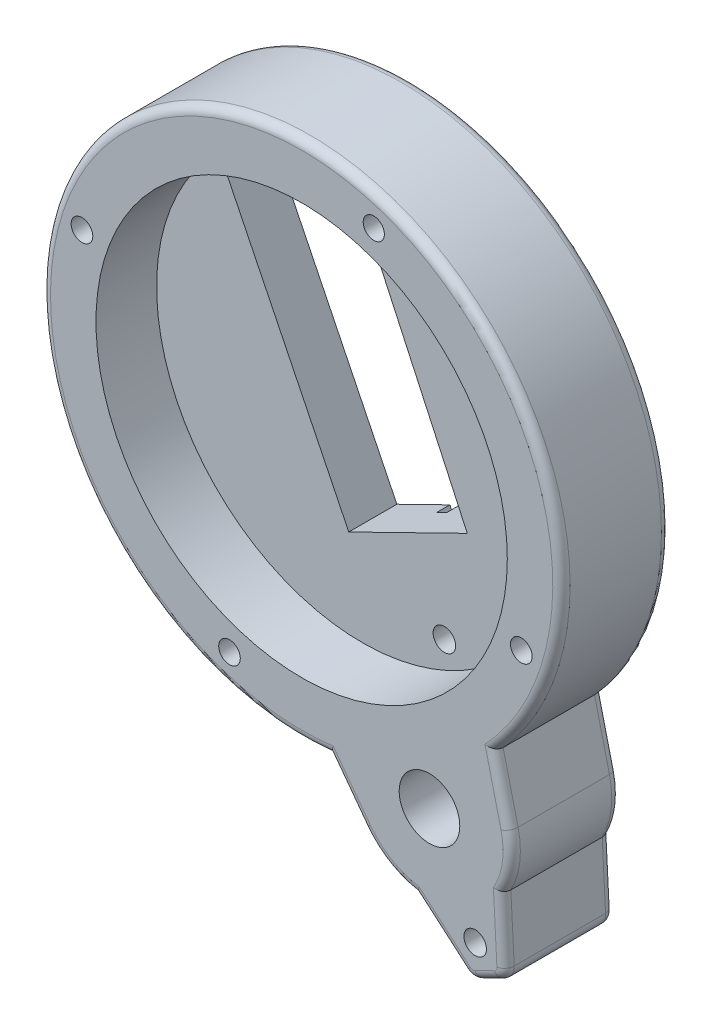
SolidWorks part; units mm, degrees
ref_plane "Front Plane" through (0, 0, 0) normal (0, 0, 1) x (1, 0, 0)
ref_plane "Top Plane" through (0, 0, 0) normal (0, 1, 0) x (1, 0, 0)
ref_plane "Right Plane" through (0, 0, 0) normal (1, 0, 0) x (0, 0, -1)
sketch "Sketch1" plane through (0, 0, 0) normal (0, 0, 1) x (1, 0, 0)
  circle A0 centre (0, 0) radius 60
  dimension "D1" = 120
extrude "Boss-Extrude1" add sketch "Sketch1" along normal blind 25.1
sketch "Sketch2" plane through (0, 0, 25.1) normal (0, 0, 1) x (1, 0, 0)
  circle A0 centre (-16.6647, -50.7331) radius 2.495
  circle A1 centre (-50.7331, 16.6647) radius 2.5
  circle A2 centre (16.6647, 50.7331) radius 2.4444
  circle A3 centre (50.7331, -16.6647) radius 2.5
sketch "Sketch3" plane through (0, 0, 25.1) normal (0, 0, 1) x (1, 0, 0)
  circle A0 centre (0, 0) radius 47.5
  dimension "D1" = 95
extrude "Cut-Extrude2" cut sketch "Sketch3" against normal blind 14
extrude "Cut-Extrude5" cut sketch "Sketch2" against normal through all both and the other way through all
sketch "Sketch6" plane through (0, 0, 0) normal (0, 0, -1) x (-1, 0, 0)
  circle A0 centre (11.9735, 47.2126) radius 3
  circle A1 centre (27.3813, 40.0293) radius 3
  circle A2 centre (-19.7177, -20.7629) radius 3
  circle A3 centre (-4.3099, -27.9462) radius 3
  dimension "D1" = 6
  dimension "D2" = 6
  dimension "D3" = 6
  dimension "D4" = 6
extrude "Cut-Extrude6" cut sketch "Sketch6" against normal blind 6
sketch "Sketch7" plane through (0, 0, 11.1) normal (0, 0, 1) x (1, 0, 0)
  line L0 (-32.4009, 32.8719) -> (-3.109, -26.9124)
  line L1 (-3.109, -26.9124) -> (24.2542, -13.5055)
  line L2 (24.2542, -13.5055) -> (-3.6508, 46.9583)
  line L3 (-3.6508, 46.9583) -> (-32.4009, 32.8719)
  circle A0 centre (0, 0) radius 47.1 construction
extrude "Cut-Extrude7" cut sketch "Sketch7" against normal through all both and the other way through all
ref_plane "Plane1" through (33.538, -68.4503, 0) normal (0.44, -0.898, 0) x (-0.898, -0.44, 0)
sketch "Sketch8" plane through (33.538, -68.4503, 0) normal (0.44, -0.898, 0) x (-0.898, -0.44, 0)
  line L1 (-12.4, 0) -> (12.4, 0)
  line L2 (-12.4, 0) -> (-12.4, -25.1)
  line L3 (-12.4, -25.1) -> (12.4, -25.1)
  line L4 (12.4, 0) -> (12.4, -25.1)
  line L5 (-12.4, 0) -> (12.4, -25.1) construction
  line L6 (-12.4, -25.1) -> (12.4, 0) construction
  point P0 (0, -12.55)
  point P5 (0, 0)
  point P6 (0, 0)
  dimension "D1" = 24.8
  dimension "D2" = 25.1
extrude "Boss-Extrude2" add sketch "Sketch8" along normal blind 22 and the other way blind 23
sketch "Sketch12" plane through (0, 0, 0) normal (0, 0, -1) x (-1, 0, 0)
  line L0 (16.5698, 40.6285) -> (19.584, 46.7804)
  line L1 (3.6508, 46.9583) -> (32.4009, 32.8719) construction
  line L2 (19.584, 46.7804) -> (22.1828, 45.5071)
  line L3 (22.1828, 45.5071) -> (19.1686, 39.3552)
  line L4 (19.1686, 39.3552) -> (16.5698, 40.6285)
  line L5 (-11.4581, -19.7751) -> (-14.3908, -26.3385)
  line L6 (3.109, -26.9124) -> (-24.2542, -13.5055) construction
  line L7 (-14.3908, -26.3385) -> (-12.0521, -27.3835)
  line L8 (-12.0521, -27.3835) -> (-9.1563, -20.9029)
  line L9 (-9.1563, -20.9029) -> (-11.4581, -19.7751)
extrude "Cut-Extrude9" cut sketch "Sketch12" against normal blind 3
sketch "Sketch13" plane through (0, 0, 0) normal (0, 0, -1) x (-1, 0, 0)
  line L0 (-36.9645, -47.2612) -> (-46.6764, -67.083)
  line L1 (-36.9645, -47.2612) -> (-36.8661, -47.0603)
  line L2 (-14.2903, -70.2734) -> (-6.2238, -59.4562)
  line L3 (-36.9645, -47.2612) -> (-54.3529, -82.7506) construction
  line L4 (-14.694, -58.1729) -> (-23.9591, -77.0828)
  line L5 (-14.694, -58.1729) -> (-32.0824, -93.6623) construction
  line L6 (-47.9852, -54.4324) -> (-44.4696, -39.9529)
  line L7 (-14.694, -58.1729) -> (-14.5879, -57.9739)
  arc A1 (-47.9852, -54.4324) -> (-46.6764, -67.083) centre (-29.5216, -58.9153) ccw
  arc A3 (-23.9591, -77.0828) -> (-14.2903, -70.2734) centre (-29.5216, -58.9153) ccw
  arc A6 (-44.4696, -39.9529) -> (-36.8661, -47.0603) centre (0, 0) ccw
  arc A7 (-14.5879, -57.9739) -> (-6.2238, -59.4562) centre (0, 0) ccw
extrude "Boss-Extrude3" add sketch "Sketch13" against normal blind 25.1
fillet "Fillet1" radius 10 2 edges at (32.0824, -93.6623, 12.55) (54.3529, -82.7506, 12.55)
sketch "Sketch14" plane through (0, 0, 0) normal (0, 0, -1) x (-1, 0, 0)
  line L0 (-23.9591, -77.0828) -> (-31.8944, -93.5468)
  line L1 (-31.8944, -93.5468) -> (-55.6373, -86.9777)
  line L2 (-55.6373, -86.9777) -> (-56.6652, -86.6933)
  line L3 (-46.6764, -67.083) -> (-56.6652, -86.6933)
  line L4 (-26.2448, -77.6306) -> (-37.6199, -87.4397)
  line L5 (-40.8991, -87.8617) -> (-45.4233, -85.6451)
  line L6 (-46.3189, -67.7951) -> (-47.1033, -82.951)
  arc A0 (-46.6764, -67.083) -> (-46.3189, -67.7951) centre (-29.5216, -58.9153) ccw
  arc A1 (-40.8991, -87.8617) -> (-37.6199, -87.4397) centre (-39.5791, -85.1677) ccw
  arc A2 (-47.0873, -82.6413) -> (-45.4233, -85.6451) centre (-44.1033, -82.951) ccw
  arc A3 (-26.2448, -77.6306) -> (-23.9591, -77.0828) centre (-29.5216, -58.9153) ccw
  line M3 (-45.3729, -87.1505) -> (-41.0625, -89.2624)
  arc M4 (-41.0625, -89.2624) -> (-27.6826, -84.6822) centre (-36.6626, -80.2824) ccw
  line M5 (-27.6826, -84.6822) -> (-23.9591, -77.0828)
  line M11 (-46.6764, -67.083) -> (-49.9531, -73.7705)
  arc M12 (-49.9531, -73.7705) -> (-45.3729, -87.1505) centre (-40.973, -78.1704) ccw
extrude "Cut-Extrude10" cut sketch "Sketch14" against normal blind 31 contours A3 L4 A1 L5 A2 L6 A0 M11 M12 M3 M4 M5 region at (26.1406, -80.7258, 0)
sketch "Sketch15" plane through (0, 0, 0) normal (0, 0, -1) x (-1, 0, 0)
  circle A0 centre (-18.9619, -37.3632) radius 2.6
  circle A1 centre (-29.5216, -58.9153) radius 7
  circle A2 centre (-40.0813, -80.4674) radius 2.6
  dimension "D1" = 5.2
  dimension "D2" = 14
  dimension "D3" = 5.2
extrude "Cut-Extrude11" cut sketch "Sketch15" against normal blind 32
fillet "Fillet3" radius 2 20 edges at (10.3331, -64.9668, 25.1) (46.7275, -84.4048, 25.1) (31.9324, -82.5351, 25.1) (39.1961, -88.1432, 25.1) (48.3756, -61.2663, 25.1) (48.3756, -61.2663, 0) (46.7275, -84.4048, 0) (43.1612, -86.7534, 0) (39.1961, -88.1432, 0) (19.5632, -75.0964, 0) (19.5632, -75.0964, 25.1) (43.1612, -86.7534, 25.1) (46.7031, -75.2182, 25.1) (46.2587, -47.3215, 25.1) (-27.2486, 53.4557, 25.1) (46.7031, -75.2182, 0) (46.2587, -47.3215, 0) (31.9324, -82.5351, 0) (-27.2486, 53.4557, 0) (10.3331, -64.9668, 0)
